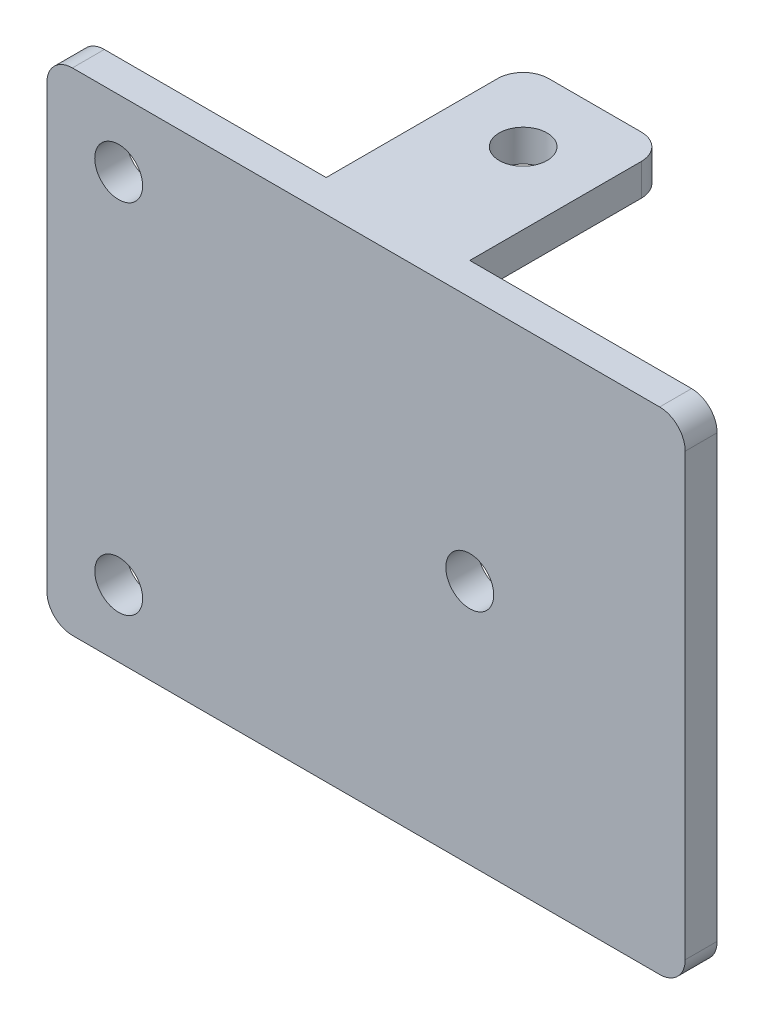
SolidWorks part; units mm, degrees
material "6061 Alloy"
ref_plane "Front Plane" through (0, 0, 0) normal (0, 0, 1) x (1, 0, 0)
ref_plane "Top Plane" through (0, 0, 0) normal (0, 1, 0) x (1, 0, 0)
ref_plane "Right Plane" through (0, 0, 0) normal (1, 0, 0) x (0, 0, -1)
sketch "Sketch1" plane through (0, 0, 0) normal (0, 0, 1) x (1, 0, 0)
  line L1 (0, 0) -> (63.5, 0)
  line L2 (0, 0) -> (0, 48.895)
  line L3 (0, 48.895) -> (63.5, 48.895)
  line L4 (63.5, 0) -> (63.5, 48.895)
  dimension "D1" = 63.5
  dimension "D2" = 48.895
extrude "Boss-Extrude1" add sketch "Sketch1" along normal blind 3.175
sketch "Sketch4" plane through (0, 0, 3.175) normal (0, 0, 1) x (1, 0, 0)
  line L0 (0, 0) -> (63.5, 0) construction
  line L1 (0, 48.895) -> (0, 0) construction
  line L2 (63.5, 24.4475) -> (0, 24.4475) construction
  line L3 (63.5, 0) -> (63.5, 48.895) construction
  line L4 (31.75, 0) -> (31.75, 48.895) construction
  line L5 (63.5, 48.895) -> (0, 48.895) construction
  circle A0 centre (7.1438, 6.6675) radius 2.3813
  circle A1 centre (7.1438, 42.2275) radius 2.3812
  circle A3 centre (42.0688, 24.4475) radius 2.3812
  circle A4 centre (7.1438, 6.6675) radius 6.35
  point P16 (44.45, 24.4475)
  point P17 (39.6875, 24.4475)
  dimension "D1" = 4.7625
  dimension "D2" = 12.7
  dimension "D4" = 19.05
  dimension "D3" = 4.7625
  dimension "D5" = 34.925
  dimension "D6" = 17.78
extrude "Cut-Extrude1" cut sketch "Sketch4" against normal up to next from surface contours A0 | A1 | A3 region at (7.1438, 6.6675, 3.175) region at (7.1438, 42.2275, 3.175) region at (42.0688, 24.4475, 3.175) starting at face at (31.75, 24.4475, 3.175)
sketch "Sketch6" plane through (0, 48.895, 0) normal (0, 1, 0) x (1, 0, 0)
  line L0 (24.6062, 0) -> (24.6062, 19.5981)
  line L1 (63.5, 0) -> (0, 0) construction
  line L2 (24.6062, 19.5981) -> (38.8938, 19.5981)
  line L3 (38.8938, 19.5981) -> (38.8938, 0)
  line L4 (31.75, 19.5981) -> (31.75, 0) construction
  line L5 (24.6062, 0) -> (38.8938, 0)
  point P9 (31.75, 0)
  dimension "D1" = 14.2875
  dimension "D2" = 19.5981
extrude "Boss-Extrude3" add sketch "Sketch6" against normal blind 3.175
sketch "Sketch7" plane through (0, 48.895, 0) normal (0, 1, 0) x (1, 0, 0)
  line L0 (31.75, 19.5981) -> (31.75, 1.4238) construction
  line L1 (38.8938, 19.5981) -> (24.6062, 19.5981) construction
  circle A0 centre (31.75, 12.4544) radius 2.3812
  point P4 (31.75, 14.8356)
  point P8 (31.75, 19.5981)
  dimension "D1" = 4.7625
  dimension "D2" = 4.7625
extrude "Cut-Extrude2" cut sketch "Sketch7" against normal up to next
fillet "Fillet1" radius 2.54 6 edges at (0, 0, 1.5875) (63.5, 0, 1.5875) (0, 48.895, 1.5875) (63.5, 48.895, 1.5875) (24.6062, 47.3075, -19.5981) (38.8938, 47.3075, -19.5981)
sketch "Sketch2" plane through (0, 0, 3.175) normal (0, 0, 1) x (1, 0, 0)
  line L0 (31.75, 0) -> (31.75, 48.895)
  line L1 (2.54, 0) -> (60.96, 0) construction
  line L2 (60.96, 48.895) -> (2.54, 48.895) construction
  line L3 (63.5, 24.4475) -> (0, 24.4475)
  line L4 (63.5, 2.54) -> (63.5, 46.355) construction
  line L5 (0, 46.355) -> (0, 2.54) construction
sketch "Sketch3" plane through (0, 0, 0) normal (0, 0, -1) x (-1, 0, 0)
  line L0 (0, 24.4475) -> (-63.5, 24.4475)
  line L1 (0, 46.355) -> (0, 2.54) construction
  line L2 (-63.5, 2.54) -> (-63.5, 46.355) construction
  line L3 (-31.75, 0) -> (-31.75, 48.895)
  line L4 (-2.54, 0) -> (-60.96, 0) construction
  line L6 (-29.3688, 48.895) -> (-34.1313, 48.895) construction
